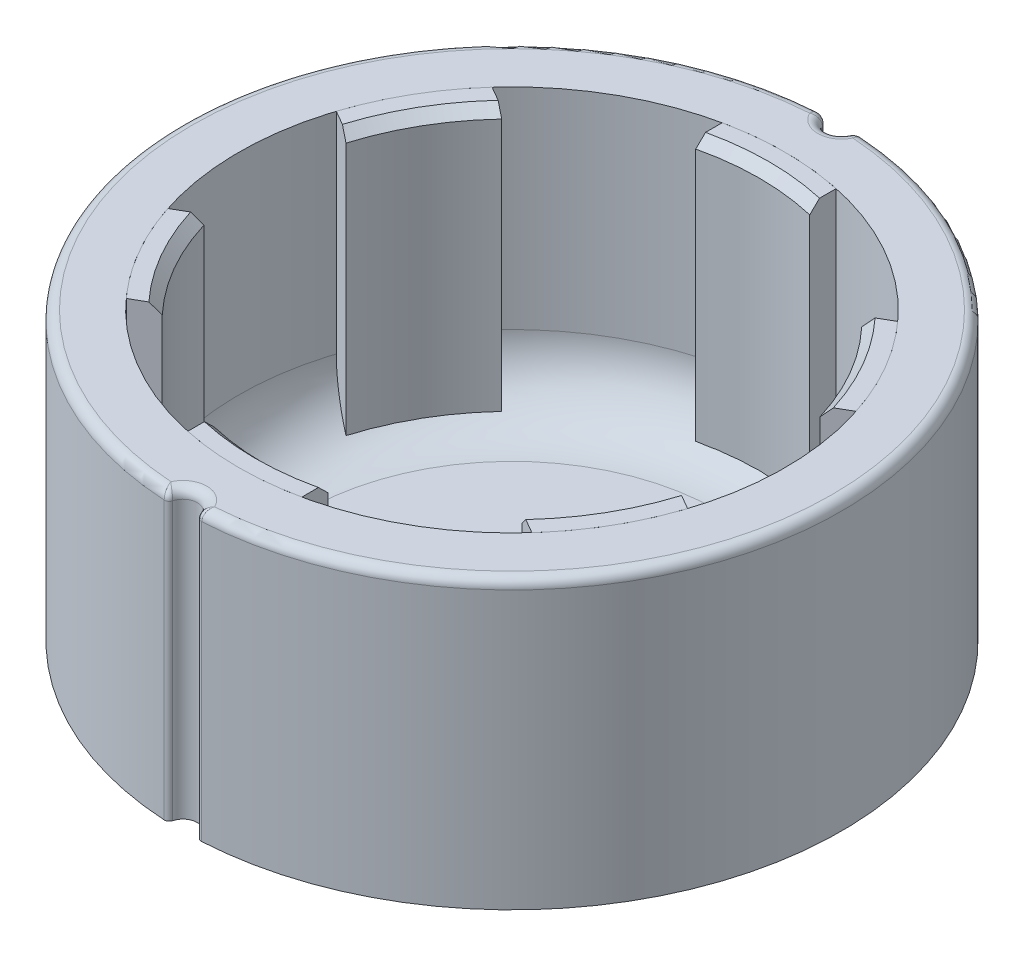
SolidWorks part; units mm, degrees
other "Markup1"
sketch "Sketch4"
other "Markup5"
sketch "Sketch8" plane through (34.5, 25, 34.4428) normal (0.0041, 0.9851, 0.1719) x (0.981, -0.0374, 0.1906)
other "Markup6"
sketch "Sketch9" plane through (34.5, 25, 34.4428) normal (0.0041, 0.9851, 0.1719) x (0.981, -0.0374, 0.1906)
other "Markup7"
sketch "Sketch10" plane through (-34.5, 25, 34.4428) normal (-0.125, 0.9874, 0.0969) x (0.5933, -0.0039, 0.805)
ref_plane "Front Plane" through (0, 0, 0) normal (0, 0, 1) x (1, 0, 0)
ref_plane "Top Plane" through (0, 0, 0) normal (0, 1, 0) x (1, 0, 0)
ref_plane "Right Plane" through (0, 0, 0) normal (1, 0, 0) x (0, 0, -1)
sketch "Sketch1" plane through (0, 0, 0) normal (0, 1, 0) x (1, 0, 0)
  line L3 (0, 0.002) -> (0, 3.7877) construction
  line L4 (0, 3.7877) -> (2.417, 3.7877)
  line L5 (0, 3.7877) -> (-2.417, 3.7877)
  arc A0 (1.9642, -34.442) -> (34.1982, 4.5552) centre (0, 0.002) ccw
  arc A2 (-2.417, 3.7877) -> (2.417, 3.7877) centre (0, 0.002) ccw
  circle A3 centre (0, 0.002) radius 34.5 construction
  arc A7 (-1.3541, 33.8562) -> (1.3541, 33.8562) centre (0, 34.5015) ccw
  arc A8 (34.1982, 4.5552) -> (2.3241, 34.4236) centre (0, 0.002) ccw
  arc A9 (-2.3241, 34.4236) -> (-34.1982, 4.5552) centre (0, 0.002) ccw
  arc A10 (-34.1982, 4.5552) -> (-1.9642, -34.442) centre (0, 0.002) ccw
  arc A11 (1.3541, 33.8562) -> (2.3241, 34.4236) centre (2.2568, 33.4259) cw
  arc A12 (-1.3541, 33.8562) -> (-2.3241, 34.4236) centre (-2.2568, 33.4259) ccw
  arc A13 (1.4518, -34.0686) -> (-1.4518, -34.0686) centre (0, -34.4457) ccw
  arc A14 (1.4518, -34.0686) -> (1.9642, -34.442) centre (1.9358, -33.9428) ccw
  arc A15 (-1.4518, -34.0686) -> (-1.9642, -34.442) centre (-1.9358, -33.9428) cw
  point P15 (1.4997, 34.4694)
  dimension "D2" = 4.834
  dimension "D3" = 4.4915
  dimension "D4" = 34.5
  dimension "D5" = 1
  dimension "D6" = 1.5
  dimension "D7" = 0.5
  dimension "D11" = 1.4997
sketch "Sketch2" plane through (0, 0, 0) normal (0, 1, 0) x (1, 0, 0)
  line L0 (0, 28.6) -> (0, 25.9) construction
  line L1 (-5.9669, 27.9706) -> (0, 28.6) construction
  line L2 (0, 28.6) -> (5.9669, 27.9706) construction
  line L3 (-5.9669, 27.9706) -> (-5.9669, 25.2033)
  line L6 (5.9669, 25.2033) -> (5.9669, 27.9706)
  circle A16 centre (0, 0) radius 28.6
  arc A18 (-5.9669, 25.2033) -> (5.9669, 25.2033) centre (0, 0) cw
  point P3 (0, 25.9)
  dimension "D1" = 57.2
  dimension "D2" = 6
  dimension "D3" = 2.7
extrude "Boss-Extrude1" add sketch "Sketch1" along normal blind 30 contours A10 A0 A8 A7 A9 A2 L5 L4 | L5 A2 L4 region at (0, 0, 0.1522) region at (2.2155, 0, 33.5591)
extrude "Cut-Extrude2" cut sketch "Sketch2" along normal up to next from offset 1 contours A16 | A16 region at (0, 0, 0.3461)
extrude "Boss-Extrude2" add sketch "Sketch2<2>" along normal up to surface (30 mm away) separate body contours A16 region at (0, 0, -27.0286) up to face at (0, 30, 28.6)
sketch "Sketch2<2>" plane through (0, 0, 0) normal (0, 1, 0) x (1, 0, 0) same geometry as "Sketch2"
chamfer "Chamfer2" distance 1 angle 45 1 edges at (0, 30, -25.9)
pattern_circular "CirPattern2" count 6 over 360 about axis through (0, 30, 0) along (0, 1, 0) of bodies 106
fillet "Fillet1" radius 1 8 edges at (-1.7518, 30, -34.2891) (0, 30, -33.0015) (1.7518, 30, -34.2891) (34.4995, 30, 0.1783) (1.6412, 30, 34.3469) (0, 30, 32.9457) (-1.6412, 30, 34.3469) (-34.4995, 30, 0.1783)
fillet "Fillet2" radius 7 1 edges at (0, 1, 28.6)
